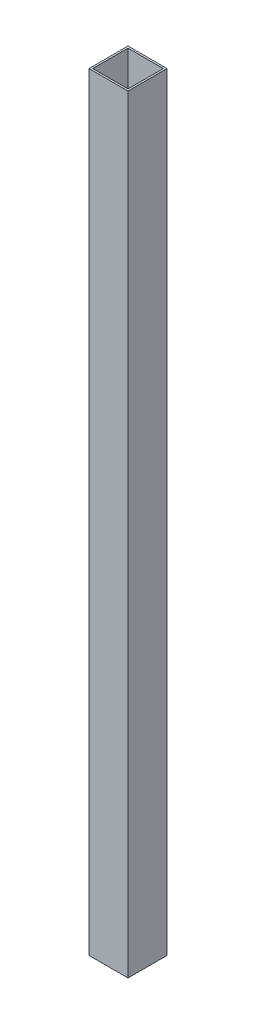
SolidWorks part; units mm, degrees
ref_plane "Front Plane" through (0, 0, 0) normal (0, 0, 1) x (1, 0, 0)
ref_plane "Top Plane" through (0, 0, 0) normal (0, 1, 0) x (1, 0, 0)
ref_plane "Right Plane" through (0, 0, 0) normal (1, 0, 0) x (0, 0, -1)
sketch "Sketch2" plane through (0, 0, 0) normal (0, 1, 0) x (1, 0, 0)
  line L0 (-11.5, 11.5) -> (11.5, 11.5)
  line L1 (-12.7, -12.7) -> (12.7, -12.7)
  line L2 (-12.7, -12.7) -> (-12.7, 12.7)
  line L3 (-12.7, 12.7) -> (12.7, 12.7)
  line L4 (12.7, -12.7) -> (12.7, 12.7)
  line L5 (-12.7, -12.7) -> (12.7, 12.7) construction
  line L6 (-12.7, 12.7) -> (12.7, -12.7) construction
  line L7 (11.5, -11.5) -> (11.5, 11.5)
  line L8 (-11.5, -11.5) -> (11.5, -11.5)
  line L9 (-11.5, -11.5) -> (-11.5, 11.5)
  point P0 (0, 0)
  dimension "D1" = 25.4
  dimension "D3" = 1.2
extrude "Boss-Extrude1" add sketch "Sketch2" along normal blind 500
